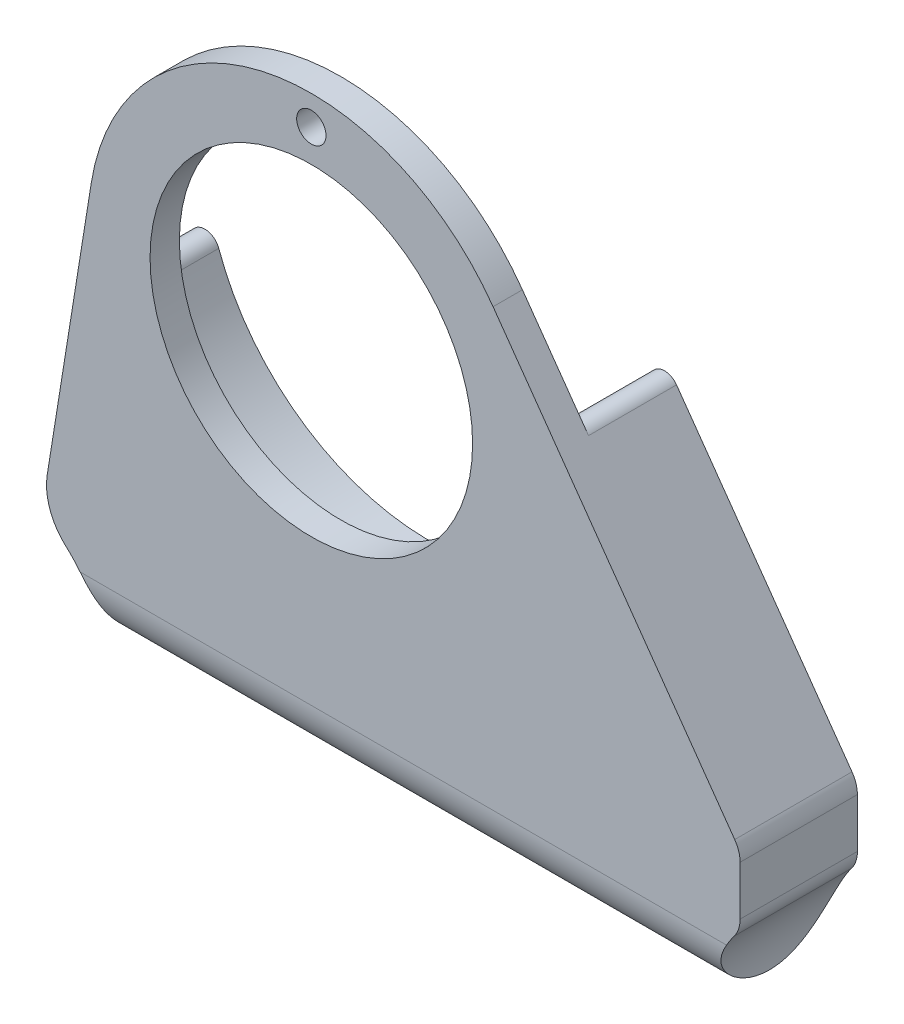
SolidWorks part; units mm, degrees
ref_plane "前视基准面" through (0, 0, 0) normal (0, 0, 1) x (1, 0, 0)
ref_plane "上视基准面" through (0, 0, 0) normal (0, 1, 0) x (1, 0, 0)
ref_plane "右视基准面" through (0, 0, 0) normal (1, 0, 0) x (0, 0, -1)
other "Configuration Table"
sketch "草图1" plane through (0, 0, 0) normal (0, 0, 1) x (1, 0, 0)
  circle A0 centre (0, 0) radius 38
  circle A1 centre (0, 0) radius 33 construction
  circle A2 centre (0, 33) radius 2.5
  circle A3 centre (0, 0) radius 27.5
  dimension "D1" = 76
  dimension "D2" = 66
  dimension "D3" = 5
  dimension "D4" = 55
extrude "凸台-拉伸1" add sketch "草图1" along normal blind 5
sketch "草图2" plane through (0, 0, 0) normal (0, 0, -1) x (-1, 0, 0)
  line L0 (-30.995, 21.9843) -> (-73.1164, -37.4014)
  line L1 (-73.1164, -37.4014) -> (-73.1164, -52.3924)
  line L2 (-73.1164, -52.3924) -> (46.8836, -52.3924)
  line L3 (46.8836, -52.3924) -> (37.521, 6.0146)
  circle A0 centre (0, 0) radius 38 construction
  arc A1 (-30.995, 21.9843) -> (37.521, 6.0146) centre (0, 0) ccw
  dimension "D1" = 120
extrude "凸台-拉伸2" add sketch "草图2" against normal blind 20
fillet "圆角2" radius 2.5 2 edges at (30.995, 21.9843, 12.5) (-37.521, 6.0146, 12.5)
fillet "圆角3" radius 10 1 edges at (-46.8836, -52.3924, 10)
fillet "圆角4" radius 5 2 edges at (73.1164, -52.3924, 10) (73.1164, -37.4014, 10)
mirror "镜向1" about plane through (0, 0, 0) normal (0, 0, 1) of "凸台-拉伸1", "圆角4", "圆角3", "圆角2", "凸台-拉伸2"
sketch "草图3" plane through (0, 0, 20) normal (0, 0, 1) x (1, 0, 0)
  line L1 (-133.1078, 81.3793) -> (133.1078, 81.3793)
  line L2 (-133.1078, 81.3793) -> (-133.1078, -81.3793)
  line L3 (-133.1078, -81.3793) -> (133.1078, -81.3793)
  line L5 (133.1078, 81.3793) -> (133.1078, -81.3793)
  line L6 (-133.1078, 81.3793) -> (133.1078, -81.3793) construction
  line L7 (-133.1078, -81.3793) -> (133.1078, 81.3793) construction
  point P0 (0, 0)
extrude "切除-拉伸1" cut sketch "草图3" against normal blind 20
sketch "草图5" plane through (0, -52.3924, 0) normal (0, -1, 0) x (1, 0, 0)
  line L0 (68.1164, -20) -> (68.1164, 0) construction
  line L1 (-35.153, 0) -> (68.1164, 0)
  line L2 (-35.153, 0) -> (-35.153, -10)
  line L3 (-35.153, -10) -> (68.1164, -10)
  line L4 (68.1164, 0) -> (68.1164, -10)
revolve "旋转1" add sketch "草图5" angle 180 about L3
fillet "圆角5" radius 20 2 edges at (68.1164, -52.3924, -10) (-35.153, -52.3924, -10)
ref_plane "基准面1" through (0, 0, -10) normal (0, 0, 1) x (1, 0, 0)
